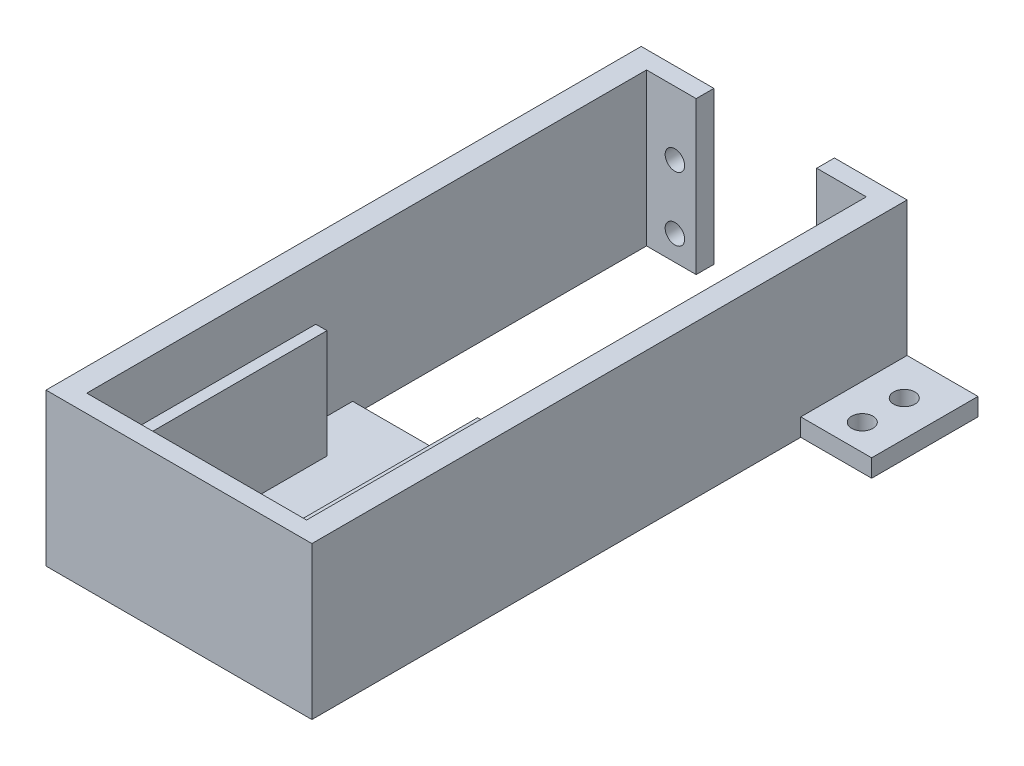
SolidWorks part; units mm, degrees
material "ABS"
ref_plane "Front Plane" through (0, 0, 0) normal (0, 0, 1) x (1, 0, 0)
ref_plane "Top Plane" through (0, 0, 0) normal (0, 1, 0) x (1, 0, 0)
ref_plane "Right Plane" through (0, 0, 0) normal (1, 0, 0) x (0, 0, -1)
sketch "Sketch1" plane through (0, 0, 0) normal (0, 0, 1) x (1, 0, 0)
  line L0 (20.5, 43) -> (20.5, 18)
  line L2 (0, 0) -> (0, 43)
  line L4 (75, 0) -> (75, 43)
  line L5 (0, 43) -> (20.5, 43)
  line L6 (54.5, 18) -> (54.5, 43)
  line L7 (37.5, 43) -> (37.5, 0) construction
  line L8 (0, 0) -> (20.5, 0)
  line L9 (20.5, 0) -> (20.5, 18)
  line L10 (54.5, 18) -> (54.5, 0)
  line L11 (54.5, 0) -> (75, 0)
  line L12 (54.5, 43) -> (75, 43)
  circle A0 centre (14.5, 25) radius 2.75
  circle A1 centre (14.5, 7) radius 2.75
  circle A2 centre (60.5, 7) radius 2.75
  circle A3 centre (60.5, 25) radius 2.75
  dimension "D6" = 5.5
  dimension "D7" = 46
  dimension "D8" = 34
  dimension "D1" = 43
  dimension "D2" = 75
  dimension "D3" = 17
  dimension "D4" = 18
  dimension "D10" = 14.5
  dimension "D11" = 6
extrude "Boss-Extrude1" add sketch "Sketch1" along normal blind 5 contours L7 L0 L2 A1 A0 | L7 L4 L6 A3 A2 region at (10.0079, 21.8134, 0) region at (64.9921, 21.8134, 0)
sketch "Sketch16" plane through (0, 0, 5) normal (0, 0, 1) x (1, 0, 0)
  line L0 (0, 41.7723) -> (6.5, 41.7723) construction
  line L1 (0, 0) -> (0, 43) construction
  line L2 (75, 41.0629) -> (68.5, 41.0629) construction
  line L3 (75, 0) -> (75, 43) construction
  line L4 (54.5, 43) -> (75, 43) construction
  line L5 (68.5, 43) -> (75, 43)
  line L6 (68.5, 43) -> (68.5, 0)
  line L7 (68.5, 0) -> (75, 0)
  line L8 (75, 43) -> (75, 0)
  line L9 (0, 43) -> (20.5, 43) construction
  line L10 (6.5, 43) -> (0, 43)
  line L11 (6.5, 43) -> (6.5, 0)
  line L12 (6.5, 0) -> (0, 0)
  line L13 (0, 43) -> (0, 0)
extrude "Boss-Extrude2" add sketch "Sketch16" along normal blind 162.9
sketch "Sketch18" plane through (68.5, 0, 0) normal (-1, 0, 0) x (0, 0, 1)
  line L0 (167.9, 0) -> (167.9, 3.5)
  line L1 (167.9, 43) -> (167.9, 0) construction
  line L2 (167.9, 3.5) -> (87.9, 3.5)
  line L3 (87.9, 3.5) -> (87.9, 0)
  line L4 (167.9, 0) -> (5, 0) construction
  line L5 (87.9, 0) -> (167.9, 0)
extrude "Boss-Extrude3" add sketch "Sketch18" along normal blind 64.9
sketch "Sketch19" plane through (68.5, 0, 0) normal (-1, 0, 0) x (0, 0, 1)
  line L0 (167.9, 3.5) -> (87.9, 3.5) construction
  line L1 (167.9, 43) -> (162.9, 43)
  line L2 (167.9, 43) -> (167.9, 3.5)
  line L3 (167.9, 3.5) -> (162.9, 3.5)
  line L4 (162.9, 43) -> (162.9, 3.5)
extrude "Boss-Extrude4" add sketch "Sketch19" along normal blind 64.9
sketch "Sketch20" plane through (0, 0, 0) normal (-1, 0, 0) x (0, 0, 1)
  line L1 (0, 0) -> (30, 0)
  line L2 (0, 0) -> (0, 5)
  line L3 (0, 5) -> (30, 5)
  line L4 (30, 0) -> (30, 5)
extrude "Boss-Extrude5" add sketch "Sketch20" along normal blind 20
sketch "Sketch21" plane through (75, 0, 0) normal (1, 0, 0) x (0, 0, -1)
  line L0 (-167.9, 0) -> (0, 0) construction
  line L1 (0, 5) -> (-30, 5)
  line L2 (0, 5) -> (0, 0)
  line L3 (0, 0) -> (-30, 0)
  line L4 (-30, 5) -> (-30, 0)
extrude "Boss-Extrude6" add sketch "Sketch21" along normal blind 20
sketch "Sketch22" plane through (0, 5, 0) normal (0, 1, 0) x (1, 0, 0)
  line L0 (-10, 0) -> (-10, -10.7991) construction
  line L1 (-20, 0) -> (0, 0) construction
  line L2 (85, 0) -> (85, -10.7991) construction
  line L3 (95, 0) -> (75, 0) construction
  line L4 (85, -10.7991) -> (85, -22.6338) construction
  line L5 (-10, -10.7991) -> (-10, -22.6338) construction
  circle A0 centre (-10, -10.7991) radius 3
  circle A1 centre (-10, -22.6338) radius 3
  circle A2 centre (85, -10.7991) radius 3
  circle A3 centre (85, -22.6338) radius 3
  dimension "D1" = 6
  dimension "D2" = 6
  dimension "D3" = 6
  dimension "D4" = 6
extrude "Cut-Extrude1" cut sketch "Sketch22" against normal blind 20
sketch "Sketch23" plane through (0, 0, 162.9) normal (0, 0, -1) x (-1, 0, 0)
sketch "Sketch24" plane through (0, 0, 162.9) normal (0, 0, -1) x (-1, 0, 0)
  line L0 (-37.5, 43) -> (-37.5, 3.5) construction
  line L1 (-6.5, 43) -> (-68.5, 43) construction
  line L2 (-6.5, 3.5) -> (-68.5, 3.5) construction
  line L3 (-37.5, 34.1387) -> (-16.25, 34.1387) construction
  line L4 (-37.5, 34.1387) -> (-58.75, 34.1387) construction
  line L10 (-58.75, 34.1387) -> (-61.8901, 34.1387)
  line L11 (-58.75, 34.1387) -> (-58.75, 3.5)
  line L12 (-58.75, 3.5) -> (-61.8901, 3.5)
  line L13 (-61.8901, 34.1387) -> (-61.8901, 3.5)
  line L14 (-16.25, 34.1387) -> (-13.11, 34.1387)
  line L15 (-16.25, 34.1387) -> (-16.25, 3.5)
  line L16 (-16.25, 3.5) -> (-13.11, 3.5)
  line L17 (-13.11, 34.1387) -> (-13.11, 3.5)
extrude "Boss-Extrude8" add sketch "Sketch24" along normal blind 58
sketch "Sketch15" plane through (0, 0, 0) normal (0, 0, -1) x (-1, 0, 0)
  line L0 (-54.5, 29.2278) -> (-75, 29.2278)
  line L1 (-54.5, 7.5) -> (-54.5, 32.5) construction
  line L2 (-75, 0) -> (-75, 32.5) construction
  line L3 (-75, 29.2278) -> (-75, 32.5)
  line L4 (-75, 32.5) -> (-54.5, 32.5)
  line L5 (-54.5, 32.5) -> (-54.5, 29.2278)
  line L6 (-20.5, 32.5) -> (-20.5, 29.2278)
  line L7 (-20.5, 32.5) -> (-20.5, 7.5) construction
  line L8 (-20.5, 29.2278) -> (0, 29.2278)
  line L9 (0, 0) -> (0, 32.5) construction
  line L10 (0, 29.2278) -> (0, 32.5)
  line L11 (0, 32.5) -> (-20.5, 32.5)
